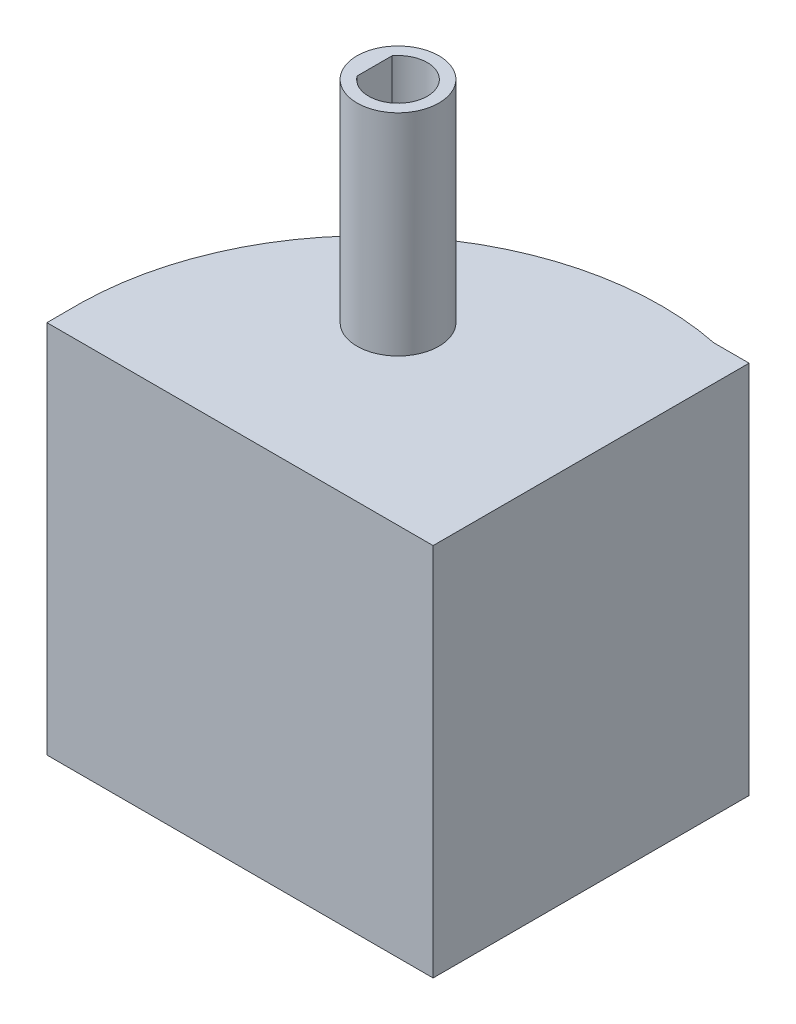
SolidWorks part; units mm, degrees
ref_plane "Front Plane" through (0, 0, 0) normal (0, 0, 1) x (1, 0, 0)
ref_plane "Top Plane" through (0, 0, 0) normal (0, 1, 0) x (1, 0, 0)
ref_plane "Right Plane" through (0, 0, 0) normal (1, 0, 0) x (0, 0, -1)
sketch "Sketch1" plane through (0, 0, 0) normal (0, 0, 1) x (1, 0, 0)
  line L0 (0, 0) -> (30, 0)
  dimension "D1" = 30
extrude "Extrude-Thin1" add sketch "Sketch1" against normal blind 24 thin thin type one direction reverse wall 3
sketch "Sketch2" plane through (0, 3, 0) normal (0, 1, 0) x (1, 0, 0)
  line L0 (0, 24) -> (30, 24) construction
  line L1 (0, 24) -> (0, 0) construction
  line L2 (18, 24) -> (18, 18.5)
  line L3 (0, 5.5) -> (5.5, 5.5)
  line L4 (30, 24) -> (30, 0) construction
  line L5 (0, 0) -> (30, 0) construction
  line L6 (18.75, 8.25) -> (11.25, 8.25)
  line L7 (0, 24) -> (0, 0)
  line L8 (0, 24) -> (30, 24)
  line L9 (18.75, 8.25) -> (18.75, 15.75)
  line L10 (18.75, 15.75) -> (11.25, 15.75)
  line L11 (11.25, 8.25) -> (11.25, 15.75)
  line L12 (18.75, 8.25) -> (11.25, 15.75) construction
  line L13 (18.75, 15.75) -> (11.25, 8.25) construction
  arc A2 (5.5, 5.5) -> (18, 18.5) centre (18.51, 5.5) cw
  point P0 (15, 12)
  line M7 (30, 24) -> (0, 24)
  line M8 (0, 24) -> (0, 0)
  dimension "D1" = 7.5
  dimension "D2" = 8.25
  dimension "D3" = 11.25
  dimension "D4" = 12
  dimension "D5" = 5.5
  dimension "D6" = 5.5
  dimension "D7" = 5.5
extrude "Cut-Extrude1" cut sketch "Sketch2" against normal through all contours L3 M7 M8 | L9 L6 L11 L10 region at (6.7319, 3, -17.0598)
fillet "Fillet1" radius 1 4 edges at (18.75, 1.5, -8.25) (11.25, 1.5, -8.25) (11.25, 1.5, -15.75) (18.75, 1.5, -15.75)
sketch "Sketch4" plane through (0, 0, 0) normal (0, -1, 0) x (1, 0, 0)
  line L0 (0, 0) -> (0, 3)
  line L1 (0, 3) -> (33, 3)
  line L2 (33, 3) -> (33, -24)
  line L3 (33, -24) -> (30, -24)
  line L4 (0, 0) -> (30, 0) construction
  line L5 (0, 0) -> (30, 0)
  line L6 (30, -24) -> (30, 0) construction
  line L7 (30, -24) -> (30, 0)
  dimension "D1" = 3
  dimension "D2" = 3
extrude "Boss-Extrude1" add sketch "Sketch4" against normal blind 32
sketch "Sketch6" plane through (0, 32, 0) normal (0, 1, 0) x (1, 0, 0)
  line L0 (0, 0) -> (30, 0) construction
  line L1 (0, 0) -> (30, 0)
  line L2 (30, 0) -> (30, 24) construction
  line L3 (30, 0) -> (30, 24)
  arc A0 (0, 0) -> (30, 24) centre (24.9951, -0.4939) cw
  dimension "D1" = 25
extrude "Boss-Extrude2" add sketch "Sketch6" against normal blind 3
sketch "Sketch7" plane through (0, 32, 0) normal (0, 1, 0) x (1, 0, 0)
  line L0 (30, 24) -> (33, 24) construction
  line L1 (13, 13.5) -> (13, 10.5)
  arc A0 (13, 10.5) -> (13, 13.5) centre (15, 12) ccw
  circle A1 centre (15, 12) radius 3.5
  dimension "D1" = 5
  dimension "D3" = 12
  dimension "D4" = 7
  dimension "D2" = 15
  dimension "D5" = 3
extrude "Boss-Extrude3" add sketch "Sketch7" along normal blind 18
